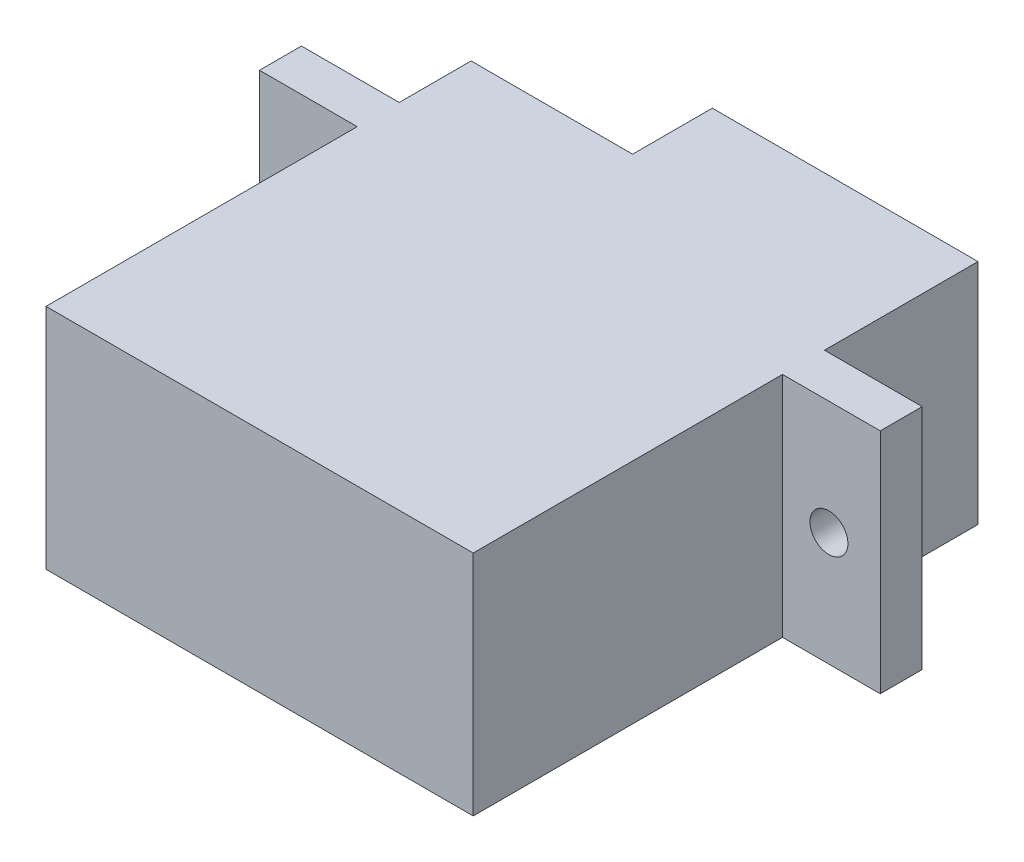
SolidWorks part; units mm, degrees
ref_plane "Front Plane" through (0, 0, 0) normal (0, 0, 1) x (1, 0, 0)
ref_plane "Top Plane" through (0, 0, 0) normal (0, 1, 0) x (1, 0, 0)
ref_plane "Right Plane" through (0, 0, 0) normal (1, 0, 0) x (0, 0, -1)
sketch "Sketch1" plane through (0, 0, 0) normal (0, 1, 0) x (1, 0, 0)
  line L0 (0, 0) -> (0, 16.4)
  line L1 (0, 16.4) -> (-5.15, 16.4)
  line L2 (-5.15, 16.4) -> (-5.15, 18.61)
  line L3 (-5.15, 18.61) -> (0, 18.61)
  line L4 (0, 18.61) -> (0, 22.4)
  line L5 (0, 22.4) -> (8.51, 22.4)
  line L6 (8.51, 22.4) -> (8.51, 26.6)
  line L7 (8.51, 26.6) -> (22.51, 26.6)
  line L8 (22.51, 26.6) -> (22.51, 18.51)
  line L9 (22.51, 18.51) -> (27.66, 18.51)
  line L10 (27.66, 18.51) -> (27.66, 16.3)
  line L11 (27.66, 16.3) -> (22.51, 16.3)
  line L12 (22.51, 16.3) -> (22.51, 0)
  line L13 (22.51, 0) -> (0, 0)
  dimension "D1" = 16.4
  dimension "D2" = 16.3
  dimension "D3" = 22.51
  dimension "D4" = 2.21
  dimension "D5" = 2.21
  dimension "D6" = 5.15
  dimension "D7" = 5.15
  dimension "D8" = 22.4
  dimension "D9" = 26.6
  dimension "D10" = 0
  dimension "D11" = 14
extrude "Boss-Extrude1" add sketch "Sketch1" along normal blind 12
sketch "Sketch4" plane through (0, 0, -26.6) normal (0, 0, -1) x (-1, 0, 0)
  line L0 (-22.51, 6) -> (-8.51, 6) construction
  line L1 (-22.51, 12) -> (-22.51, 0) construction
  line L2 (-8.51, 12) -> (-8.51, 0) construction
  circle A0 centre (-17.01, 6) radius 2.4
  dimension "D1" = 4.8
  dimension "D2" = 5.5
extrude "Boss-Extrude3" add sketch "Sketch4" along normal blind 2.5
sketch "Sketch6" plane through (0, 0, 0) normal (0, 0, 1) x (1, 0, 0)
  line L0 (11.255, 0) -> (11.255, 12) construction
  line L1 (0, 0) -> (22.51, 0) construction
  line L2 (0, 12) -> (22.51, 12) construction
  line L3 (11.255, 6) -> (28.8536, 6) construction
  circle A0 centre (24.955, 6) radius 1
  circle A1 centre (-2.445, 6) radius 1
  dimension "D1" = 2
  dimension "D2" = 27.4
extrude "Cut-Extrude1" cut sketch "Sketch6" against normal through all
ref_axis "Rotation Axis" through (17.01, 6, -29.1) along (0, 0, 1)
